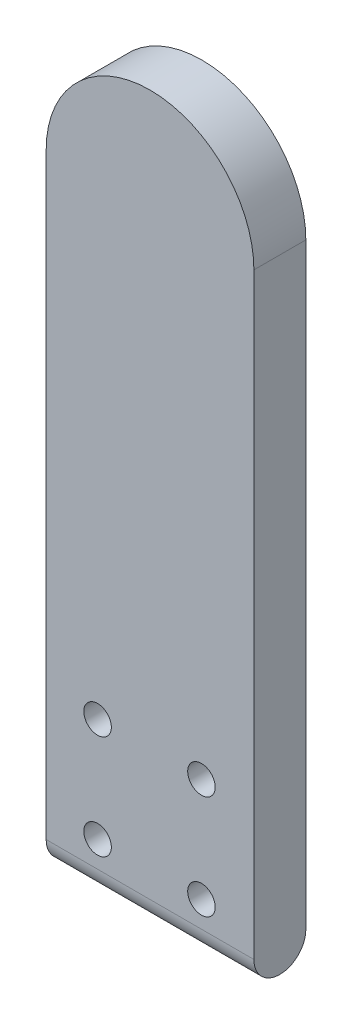
SolidWorks part; units mm, degrees
ref_plane "Front Plane" through (0, 0, 0) normal (0, 0, 1) x (1, 0, 0)
ref_plane "Top Plane" through (0, 0, 0) normal (0, 1, 0) x (1, 0, 0)
ref_plane "Right Plane" through (0, 0, 0) normal (1, 0, 0) x (0, 0, -1)
sketch "Sketch1" plane through (0, 0, 0) normal (0, 1, 0) x (1, 0, 0)
  line L1 (-35.2586, -6.1999) -> (4.7414, -6.1999)
  line L2 (-35.2586, -6.1999) -> (-35.2586, -16.1999)
  line L3 (-35.2586, -16.1999) -> (4.7414, -16.1999)
  line L4 (4.7414, -6.1999) -> (4.7414, -16.1999)
extrude "Boss-Extrude1" add sketch "Sketch1" along normal blind 140
fillet "Fillet4" 2 edges at (4.7414, 140, 11.1999) (-35.2586, 140, 11.1999) type full round first side face at (4.7414, 70, 11.1999) second side face at (-35.2586, 70, 11.1999) middle face at (-15.2586, 140, 11.1999)
sketch "Sketch2" plane through (0, 0, 6.1999) normal (0, 0, -1) x (-1, 0, 0)
  line L0 (15.2586, 140) -> (15.2586, 0) construction
  line L1 (-4.7414, 0) -> (35.2586, 0) construction
  circle A0 centre (5.3586, 10) radius 2.65
  circle A1 centre (25.3586, 10) radius 2.65
  circle A2 centre (25.3586, 30) radius 2.65
  circle A3 centre (5.3586, 30) radius 2.65
  arc A4 (35.2586, 120) -> (-4.7414, 120) centre (15.2586, 120) ccw construction
  dimension "D1" = 20
  dimension "D2" = 20
  dimension "D4" = 10
extrude "Cut-Extrude1" cut sketch "Sketch2" against normal blind 10
fillet "Fillet5" radius 5 2 edges at (-15.2586, 0, 16.1999) (-15.2586, 0, 6.1999)
